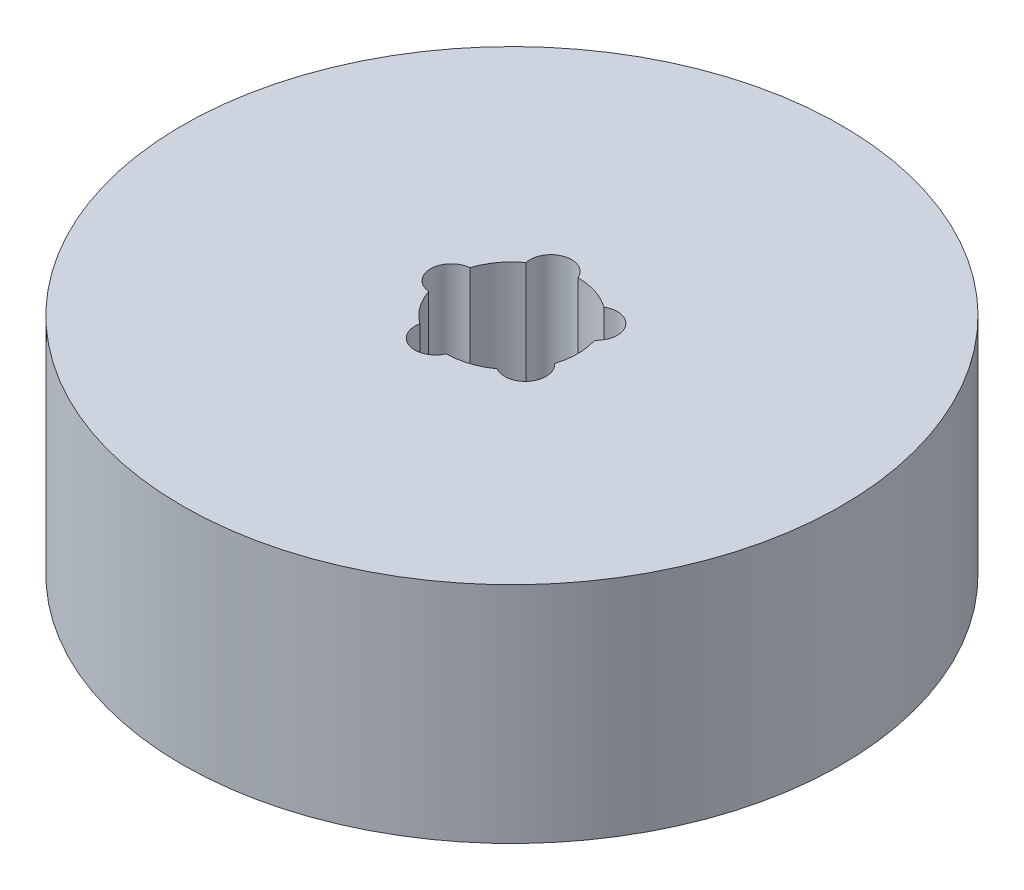
SolidWorks part; units mm, degrees
ref_plane "Front Plane" through (0, 0, 0) normal (0, 0, 1) x (1, 0, 0)
ref_plane "Top Plane" through (0, 0, 0) normal (0, 1, 0) x (1, 0, 0)
ref_plane "Right Plane" through (0, 0, 0) normal (1, 0, 0) x (0, 0, -1)
sketch "Sketch1" plane through (0, 0, 0) normal (0, 1, 0) x (1, 0, 0)
  circle A0 centre (0, 0) radius 25
  dimension "FLANGE_OD" = 50
extrude "Boss-Extrude1" add sketch "Sketch1" along normal blind 17
sketch "Sketch2" plane through (0, 0, 0) normal (0, 1, 0) x (1, 0, 0)
  circle A0 centre (0, 0) radius 5
  dimension "BORE_D" = 10
extrude "Cut-Extrude1" cut sketch "Sketch2" along normal through all
sketch "Sketch3" plane through (0, 17, 0) normal (0, 1, 0) x (1, 0, 0)
  circle A0 centre (0, 0) radius 4.5998 construction
  circle A1 centre (-4.5998, 0) radius 1.5696
  dimension "BOLT_D" = 3.1392
  dimension "BOLT_PCD" = 9.1996
extrude "Cut-Extrude2" cut sketch "Sketch3" against normal blind 11.485
pattern_circular "CirPattern1" count 5 over 360 about axis through (0, 0, 0) along (0, 1, 0) of "Cut-Extrude2"
